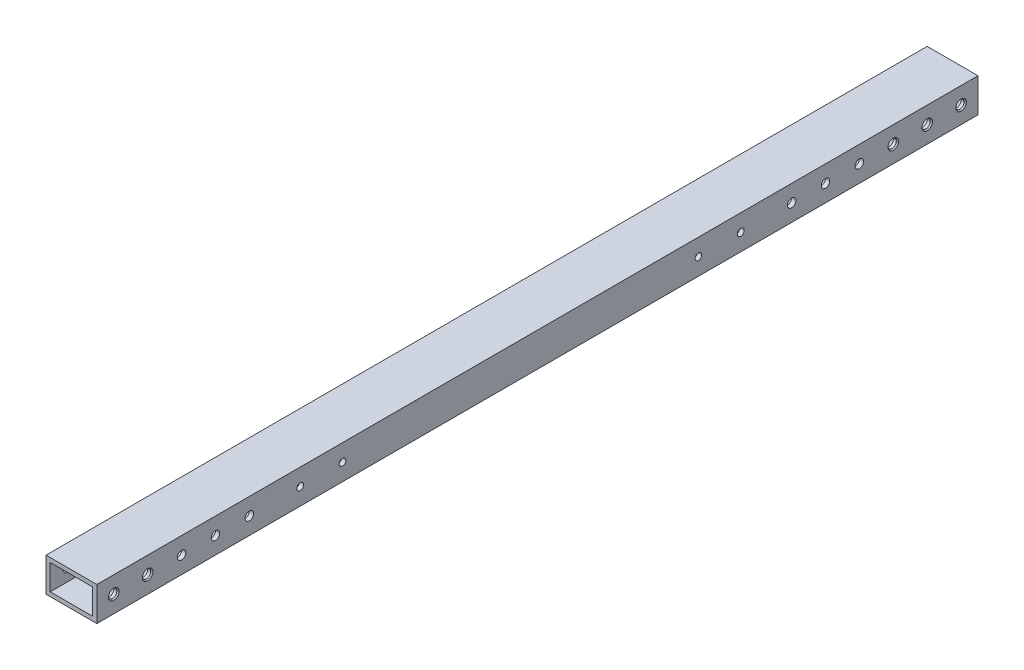
SolidWorks part; units mm, degrees
ref_plane "Front Plane" through (0, 0, 0) normal (0, 0, 1) x (1, 0, 0)
ref_plane "Top Plane" through (0, 0, 0) normal (0, 1, 0) x (1, 0, 0)
ref_plane "Right Plane" through (0, 0, 0) normal (1, 0, 0) x (0, 0, -1)
sketch "Sketch1" plane through (0, 0, 0) normal (0, 0, 1) x (1, 0, 0)
  line L0 (-15.875, 9.525) -> (15.875, 9.525)
  line L2 (-19.05, 12.7) -> (19.05, 12.7)
  line L3 (-19.05, 12.7) -> (-19.05, -12.7)
  line L4 (-19.05, -12.7) -> (19.05, -12.7)
  line L5 (19.05, 12.7) -> (19.05, -12.7)
  line L10 (15.875, 9.525) -> (15.875, -9.525)
  line L11 (-15.875, -9.525) -> (15.875, -9.525)
  line L12 (-15.875, 9.525) -> (-15.875, -9.525)
  point P12 (0, 12.7)
  point P14 (19.05, 0)
  dimension "Wall Thickness" = 3.175
  dimension "Outside Width" = 38.1
  dimension "Outside Height" = 25.4
  dimension "Inside Height" = 19.05
  dimension "Inside Width" = 31.75
sketch "Sketch2" plane through (0, 0, 0) normal (1, 0, 0) x (0, 0, -1)
  line L0 (330.2, 0) -> (-330.2, 0)
  point P4 (0, 0)
  point P7 (-330.2, 0)
  point P10 (330.2, 0)
  dimension "Length" = 660.4
sketch "Sketch3" plane through (0, 0, 0) normal (0, 0, 1) x (1, 0, 0)
  line L21 (19.05, 12.7) -> (-19.05, 12.7)
  line L22 (19.05, -12.7) -> (19.05, 12.7)
  line L23 (-19.05, -12.7) -> (19.05, -12.7)
  line L24 (-19.05, 12.7) -> (-19.05, -12.7)
  line L25 (19.05, 12.7) -> (-19.05, 12.7)
  line L26 (19.05, -12.7) -> (19.05, 12.7)
  line L27 (-19.05, -12.7) -> (19.05, -12.7)
  line L28 (-19.05, 12.7) -> (-19.05, -12.7)
  line L29 (15.875, 9.525) -> (-15.875, 9.525)
  line L30 (15.875, -9.525) -> (15.875, 9.525)
  line L31 (-15.875, -9.525) -> (15.875, -9.525)
  line L32 (-15.875, 9.525) -> (-15.875, -9.525)
  line L33 (15.875, 9.525) -> (-15.875, 9.525)
  line L34 (15.875, -9.525) -> (15.875, 9.525)
  line L35 (-15.875, -9.525) -> (15.875, -9.525)
  line L36 (-15.875, 9.525) -> (-15.875, -9.525)
  dimension "D1" = 0
  dimension "D2" = 0
extrude "Boss-Extrude1" add sketch "Sketch3" along normal up to vertex (330.2 mm away) and the other way up to vertex (330.2 mm away) up to point (0, 0, 330.2) other way up to point (0, 0, -330.2)
sketch "Drawing Reference" plane through (0, 0, 0) normal (1, 0, 0) x (0, 0, -1)
  line L0 (-330.2, 0) -> (330.2, 0) construction
  line L1 (0, -12.7) -> (0, 12.7) construction
  line L2 (-330.2, -12.7) -> (330.2, -12.7) construction
  line L5 (-330.2, 12.7) -> (330.2, 12.7) construction
  point P7 (-302.768, 0)
  point P8 (302.768, 0)
  dimension "D1" = 27.432
sketch "Sketch4" plane through (-19.05, 0, 0) normal (-1, 0, 0) x (0, 0, 1)
  line L0 (-330.2, 0) -> (-317.5, 0)
  line L1 (-330.2, 12.7) -> (-330.2, -12.7) construction
  line L2 (-317.5, 0) -> (-292.1, 0)
  line L3 (-292.1, 0) -> (-266.7, 0)
  line L4 (-266.7, 0) -> (-241.3, 0)
  line L5 (-241.3, 0) -> (-215.9, 0)
  line L6 (-215.9, 0) -> (-190.5, 0)
  line L7 (330.2, 0) -> (317.5, 0)
  line L8 (330.2, 12.7) -> (330.2, -12.7) construction
  line L9 (317.5, 0) -> (292.1, 0)
  line L10 (292.1, 0) -> (266.7, 0)
  line L11 (266.7, 0) -> (241.3, 0)
  line L12 (241.3, 0) -> (215.9, 0)
  line L13 (-190.5, 0) -> (-120.65, 0)
  line L14 (-190.5, 0) -> (-152.4, 0) construction
  line L15 (215.9, 0) -> (146.05, 0)
hole_wizard "1/4 (0.25) Diameter Hole2" positions "Sketch7" profile "Sketch8" hole size "1/4" standard "ANSI Inch" end condition through all
sketch "Sketch7" plane through (-19.05, 0, 0) normal (-1, 0, 0) x (0, 0, 1)
  point P0 (-317.5, 0)
  point P3 (-292.1, 0)
  point P7 (317.5, 0)
  point P11 (-266.7, 0)
  point P14 (292.1, 0)
sketch "Sketch8" plane through (-19.05, 0, -317.5) normal (0, 1, 0) x (0, 0, 1)
  line L0 (0, 0) -> (0, 38.1)
  line L1 (0, 38.1) -> (3.9624, 38.1)
  line L2 (3.175, 37.1942) -> (3.175, 0)
  line L5 (3.175, 0) -> (0, 0)
  line L7 (3.9624, 38.1) -> (3.175, 37.1942)
  line L8 (-3.9624, 38.1) -> (-3.175, 37.1942) construction
  line L11 (0, -6.35) -> (0, 107.95) construction
  dimension "Thru Hole Dia." = 6.35
  dimension "Thru Hole Depth" = 38.1
  dimension "Far C'Sink Dia." = 7.9248
  dimension "Far C'Sink Angle" = 82
hole_wizard "1/4 (0.25) Diameter Hole3" positions "Sketch9" profile "Sketch10" hole size "1/4" standard "ANSI Inch" end condition through all
sketch "Sketch9" plane through (19.05, 0, 0) normal (1, 0, 0) x (0, 0, -1)
  point P0 (-266.7, 0)
  point P3 (-241.3, 0)
  point P6 (-215.9, 0)
  point P9 (241.3, 0)
  point P12 (215.9, 0)
  point P15 (190.5, 0)
sketch "Sketch10" plane through (19.05, 0, 266.7) normal (0, 1, 0) x (0, 0, -1)
  line L0 (0, 0) -> (0, 38.1)
  line L1 (0, 38.1) -> (3.175, 38.1)
  line L2 (3.175, 38.1) -> (3.175, 0)
  line L5 (3.175, 0) -> (0, 0)
  line L11 (0, -6.35) -> (0, 107.95) construction
  dimension "Thru Hole Dia." = 6.35
  dimension "Thru Hole Depth" = 38.1
hole_wizard "13/64 (0.20313) Diameter Hole1" positions "Sketch11" profile "Sketch12" hole size "13/64" standard "ANSI Inch" end condition through all
sketch "Sketch11" plane through (19.05, 0, 0) normal (1, 0, 0) x (0, 0, -1)
  point P0 (152.4, 0)
  point P7 (-177.8, 0)
sketch "Sketch12" plane through (19.05, 0, -152.4) normal (0, 1, 0) x (0, 0, -1)
  line L0 (0, 0) -> (0, 38.1)
  line L1 (0, 38.1) -> (2.5798, 38.1)
  line L2 (2.5798, 38.1) -> (2.5798, 0)
  line L5 (2.5798, 0) -> (0, 0)
  line L11 (0, -6.35) -> (0, 107.95) construction
  dimension "Thru Hole Dia." = 5.1595
  dimension "Thru Hole Depth" = 38.1
hole_wizard "#10 Clearance Hole1" positions "Sketch13" profile "Sketch14" hole size "#10" standard "ANSI Inch" end condition through all
sketch "Sketch13" plane through (-19.05, 0, 0) normal (-1, 0, 0) x (0, 0, 1)
  point P0 (-120.65, 0)
  point P3 (146.05, 0)
sketch "Sketch14" plane through (-19.05, 0, -120.65) normal (0, 1, 0) x (0, 0, 1)
  line L0 (0, 0) -> (0, 38.1)
  line L1 (0, 38.1) -> (2.4892, 38.1)
  line L2 (2.4892, 38.1) -> (2.4892, 0)
  line L5 (2.4892, 0) -> (0, 0)
  line L11 (0, -6.35) -> (0, 107.95) construction
  dimension "Thru Hole Dia." = 4.9784
  dimension "Thru Hole Depth" = 38.1
equation "\"D1@Drawing Reference\"=\"Outside Width@Sketch1\" * 0.72"
